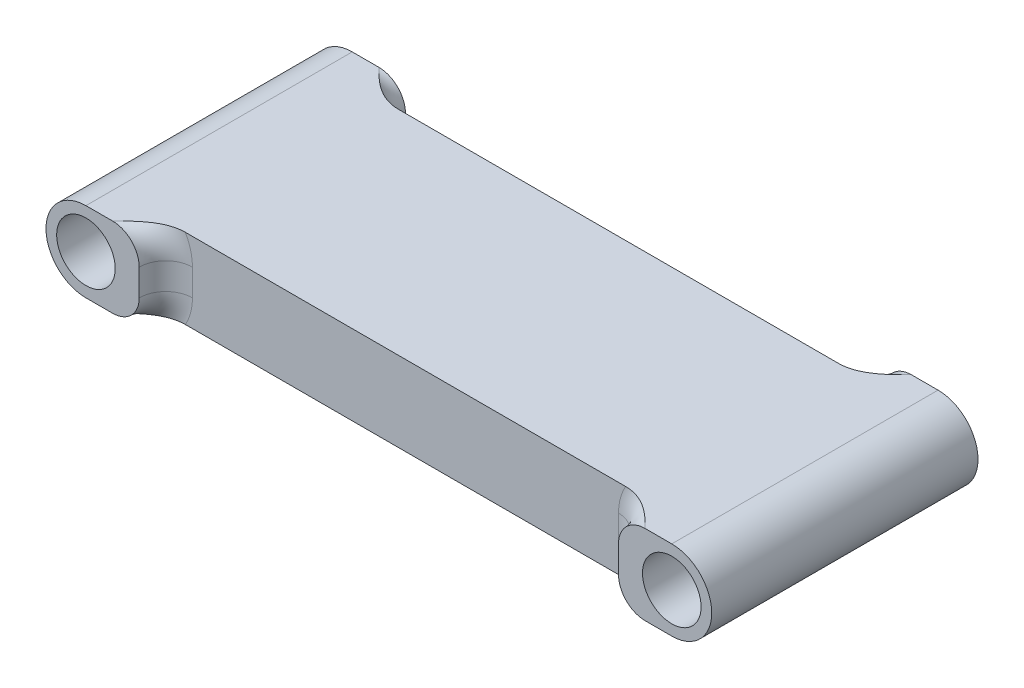
SolidWorks part; units mm, degrees
ref_plane "Plan de face" through (0, 0, 0) normal (0, 0, 1) x (1, 0, 0)
ref_plane "Plan de dessus" through (0, 0, 0) normal (0, 1, 0) x (1, 0, 0)
ref_plane "Plan de droite" through (0, 0, 0) normal (1, 0, 0) x (0, 0, -1)
sketch "Sketch1" plane through (0, 0, 0) normal (0, 0, 1) x (1, 0, 0)
  line L0 (55, 0) -> (-55, 0) construction
  line L5 (55, -7.5) -> (-55, -7.5)
  line L6 (55, 7.5) -> (-55, 7.5)
  arc A0 (55, -7.5) -> (55, 7.5) centre (55, 0) ccw
  arc A1 (-55, 7.5) -> (-55, -7.5) centre (-55, 0) ccw
  circle A2 centre (-55, 0) radius 5.5
  circle A4 centre (55, 0) radius 5.5
  point P0 (0, 0)
  point P3 (0, 0)
  dimension "D2" = 7.5
  dimension "D3" = 11
  dimension "D4" = 11
  dimension "D1" = 110
extrude "Boss-Extrude1" add sketch "Sketch1" along normal mid plane 50
sketch "Sketch2" plane through (0, 0, -25) normal (0, 0, -1) x (-1, 0, 0)
  line L0 (55, 0) -> (-55, 0) construction
  line L1 (55, -7.5) -> (-55, -7.5)
  line L2 (55, 7.5) -> (-55, 7.5)
  arc A0 (55, -7.5) -> (55, 7.5) centre (55, 0) ccw
  arc A1 (-55, 7.5) -> (-55, -7.5) centre (-55, 0) ccw
  arc A2 (-55, 7.5) -> (-55, -7.5) centre (-55, 0) ccw construction
  point P2 (0, 0)
extrude "Boss-Extrude2" add sketch "Sketch2" against normal blind 30 from offset 10 offset against normal yes
sketch "Sketch3" plane through (0, 7.5, 0) normal (0, 1, 0) x (1, 0, 0)
  line L0 (-45, 20) -> (-45, 25)
  line L1 (45, -20) -> (-45, -20)
  line L2 (45, -20) -> (45, 20)
  line L3 (45, 20) -> (-45, 20)
  line L4 (-45, -20) -> (-45, 20)
  line L5 (45, -20) -> (-45, 20) construction
  line L6 (45, 20) -> (-45, -20) construction
  line L7 (-45, 25) -> (-45, -25)
  line L9 (45, 25) -> (45, -25)
  line L15 (55, 25) -> (-55, 25)
  line L16 (-55, 25) -> (-55, -25)
  line L17 (-55, -25) -> (55, -25)
  line L18 (55, -25) -> (55, 25)
  line L19 (55, 25) -> (-55, 25)
  line L20 (-55, 25) -> (-55, -25)
  line L21 (-55, -25) -> (55, -25)
  line L22 (55, -25) -> (55, 25)
  point P0 (0, 0)
  dimension "D1" = 40
  dimension "D2" = 90
  dimension "D3" = 0
extrude "Cut-Extrude1" cut sketch "Sketch3" against normal through all both and the other way through all
fillet "Fillet1" radius 5 8 edges at (45, -7.5, 22.5) (45, 7.5, 22.5) (-45, -7.5, 22.5) (-45, 7.5, 22.5) (45, -7.5, -22.5) (45, 7.5, -22.5) (-45, 7.5, -22.5) (-45, -7.5, -22.5)
fillet "Fillet2" radius 5 12 edges at (46.4645, -6.0355, -20) (46.4645, 6.0355, -20) (-46.4645, -6.0355, -20) (-46.4645, 6.0355, -20) (-46.4645, -6.0355, 20) (-46.4645, 6.0355, 20) (46.4645, -6.0355, 20) (45, 0, 20) (45, 0, -20) (-45, 0, -20) (-45, 0, 20) (46.4645, 6.0355, 20)
